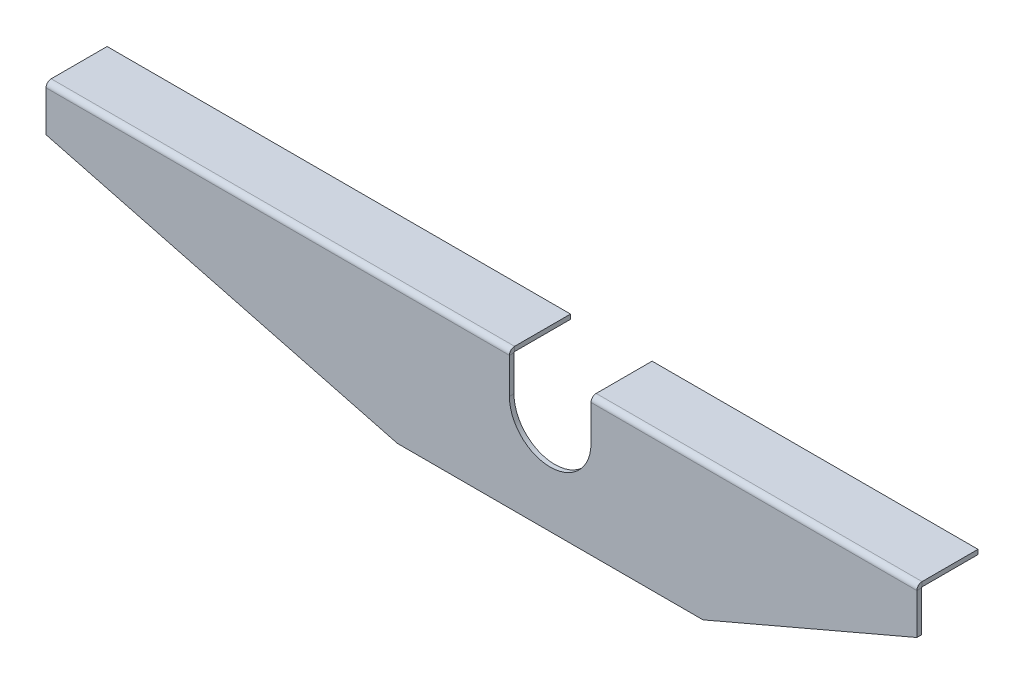
SolidWorks part; units mm, degrees
note: The reader was unsure of these and kept them because the rebuilt part matched: flange length of "Edge-Flange1".
material "Galvanized Steel"
ref_plane "Front Plane" through (0, 0, 0) normal (0, 0, 1) x (1, 0, 0)
ref_plane "Top Plane" through (0, 0, 0) normal (0, 1, 0) x (1, 0, 0)
ref_plane "Right Plane" through (0, 0, 0) normal (1, 0, 0) x (0, 0, -1)
sketch "Sketch1" plane through (0, 0, 0) normal (0, 0, 1) x (1, 0, 0)
  line L0 (13.35, 0) -> (13.35, 13.35)
  line L1 (13.35, 13.35) -> (120, 13.35)
  line L2 (120, 13.35) -> (120, -1.65)
  line L3 (120, -1.65) -> (50, -31.65)
  line L4 (50, -31.65) -> (-50, -31.65)
  line L5 (-50, -31.65) -> (-165, -1.65)
  line L6 (-165, -1.65) -> (-165, 13.35)
  line L7 (-165, 13.35) -> (-13.35, 13.35)
  line L8 (-13.35, 13.35) -> (-13.35, 0)
  arc A0 (-13.35, 0) -> (13.35, 0) centre (0, 0) ccw
  point P1 (0, -31.65)
  dimension "D1" = 26.7
  dimension "D2" = 100
  dimension "D3" = 0
  dimension "D4" = 15
  dimension "D5" = 15
  dimension "D6" = 165
  dimension "D7" = 120
  dimension "D8" = 45
base flange "Base-Flange1" sketch "Sketch1" thickness 1.5 reverse thickness direction no parameters "D1"=0.2
edge flange "Edge-Flange1" sketch "Sketch10" flange profiles "Sketch10", "Sketch11" flange angle 90 flange length 20 flange position material inside bend radius 0.2 thickness 1.5 relief rectangular parameters "D6"=10, "D8"=1
sketch "Sketch10" plane through (0, 13.35, -1.5) normal (0, -1, 0) x (-1, 0, 0)
  line L2 (13.35, 0) -> (13.35, 18.5)
  line L3 (13.35, 18.5) -> (165, 18.5)
  line L4 (165, 18.5) -> (165, 0)
  line L5 (165, 0) -> (13.35, 0) construction
  line L8 (165, 0) -> (13.35, 0)
sketch "Sketch11" plane through (0, 13.35, -1.5) normal (0, -1, 0) x (-1, 0, 0)
  line L2 (-120, 0) -> (-120, 18.5)
  line L3 (-120, 18.5) -> (-13.35, 18.5)
  line L4 (-13.35, 18.5) -> (-13.35, 0)
  line L5 (-13.35, 0) -> (-120, 0) construction
  line L8 (-13.35, 0) -> (-120, 0)
bend "EdgeBend1" bend radius 0.2 bend angle 90 parameters "D5"=1
bend "EdgeBend2" bend radius 0.2 bend angle 90 parameters "D5"=2
sketch "Bend-Lines1" [suppressed] plane through (0, 0, 0) normal (0, 1, 0) x (1, 0, 0)
sketch "Bounding-Box1" [suppressed] plane through (0, 0, 0) normal (0, 1, 0) x (1, 0, 0)
sheet metal parameters "Sheet-Metal1" thickness 1.5 parameters "D1"=0.2
flat pattern "Flat-Pattern1" [suppressed]
sketch "Bend-Lines2" plane through (0, 0, 0) normal (0, 1, 0) x (1, 0, 0)
sketch3d "Bounding-Box2" [suppressed]
  line L0 (350, -31.65, 0) -> (-350, -31.65, 0) construction
  line L1 (350, 13.35, 0) -> (-350, 13.35, 0) construction
  line L2 (350, -31.65, 0) -> (350, 13.35, 0) construction
  line L3 (-350, -31.65, 0) -> (-350, 13.35, 0) construction
sheet metal parameters "Sheet-Metal2" thickness 1.5 parameters "D1"=0.2
flat pattern "Flat-Pattern1"
sketch "Bend-Lines2" plane through (0, 0, 0) normal (0, 0, 1) x (1, 0, 0)
  line L0 (120, 12.3961) -> (13.35, 12.3961) construction
  line L1 (-13.35, 12.3961) -> (-165, 12.3961) construction
  line L2 (120, 12.3961) -> (13.35, 12.3961) construction
  line L3 (-13.35, 12.3961) -> (-165, 12.3961) construction
sketch3d "Bounding-Box2" [suppressed]
  line L0 (-165, -31.65, 0) -> (120, -31.65, 0) construction
  line L1 (-165, 31.4423, 0) -> (120, 31.4423, 0) construction
  line L2 (-165, -31.65, 0) -> (-165, 31.4423, 0) construction
  line L3 (120, -31.65, 0) -> (120, 31.4423, 0) construction
bend of the flat pattern "Flatten-<EdgeBend1>1"
bend of the flat pattern "Flatten-<EdgeBend2>1"
